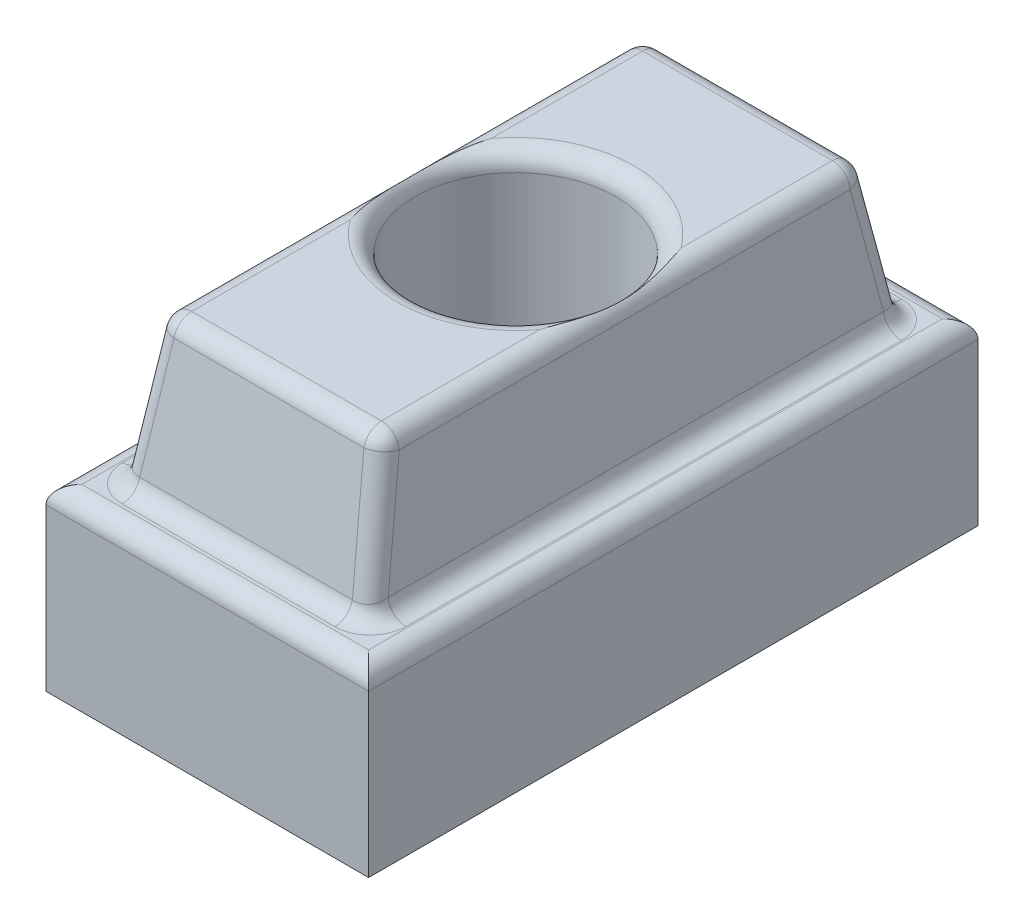
SolidWorks part; units mm, degrees
ref_plane "前视基准面" through (0, 0, 0) normal (0, 0, 1) x (1, 0, 0)
ref_plane "上视基准面" through (0, 0, 0) normal (0, 1, 0) x (1, 0, 0)
ref_plane "右视基准面" through (0, 0, 0) normal (1, 0, 0) x (0, 0, -1)
other "Configuration Table"
sketch "草图1" plane through (0, 0, 0) normal (0, 1, 0) x (1, 0, 0)
  line L0 (14.5065, 0) -> (23.5065, 0)
  line L1 (23.5065, 0) -> (23.5065, 17)
  line L2 (23.5065, 17) -> (14.5065, 17)
  line L3 (14.5065, 17) -> (14.5065, 0)
extrude "凸台-拉伸1" add sketch "草图1" along normal blind 5
sketch "草图2" plane through (0, 0, 0) normal (0, 0, 1) x (1, 0, 0)
  line L1 (14.5065, 5) -> (23.5065, 5) construction
  line L2 (19.0065, 10) -> (22.0065, 10)
  line L4 (22.5065, 5) -> (22.0065, 10)
  line L6 (19.0065, 10) -> (16.0065, 10)
  line L7 (16.0065, 10) -> (15.5065, 5)
  line L8 (15.5065, 5) -> (22.5065, 5)
extrude "凸台-拉伸2" add sketch "草图2" against normal blind 17
sketch "草图3" plane through (0, 10, 0) normal (0, 1, 0) x (1, 0, 0)
  circle A0 centre (19.0065, 8.6) radius 1.6
extrude "切除-拉伸1" cut sketch "草图3" against normal through all
sketch "草图4" plane through (0, 10, 0) normal (0, 1, 0) x (1, 0, 0)
  circle A0 centre (19.0065, 8.6) radius 2.8
extrude "切除-拉伸2" cut sketch "草图4" against normal blind 6
sketch "草图5" plane through (14.5065, 0, 0) normal (-1, 0, 0) x (0, 0, 1)
  line L0 (-17, 5) -> (-16, 5)
  line L1 (-17, 5) -> (0, 5) construction
  line L2 (-17, 5) -> (-17, 10)
  line L3 (-17, 10) -> (-15, 10)
  line L4 (-17, 10) -> (0, 10) construction
  line L5 (-15.2, 9) -> (-16, 5)
  line L6 (0, 5) -> (-1, 5)
  line L7 (0, 5) -> (0, 10)
  line L8 (0, 10) -> (-2, 10)
  line L9 (-1.8, 9) -> (-1, 5)
  line L11 (-8.5, 9) -> (-1.8, 9)
  line L12 (-8.5, 9) -> (-15.2, 9)
  line L13 (-2, 10) -> (-15, 10)
extrude "切除-拉伸3" cut sketch "草图5" against normal through all
fillet "圆角1" radius 0.5 17 edges at (19.0065, 9, -11.4) (19.0065, 9, -1.8) (15.9065, 9, -8.5) (19.0065, 9, -15.2) (22.1065, 9, -8.5) (19.0065, 5, -17) (23.5065, 5, -8.5) (19.0065, 5, 0) (14.5065, 5, -8.5) (19.0065, 5, -16) (15.5065, 5, -8.5) (19.0065, 5, -1) (22.5065, 5, -8.5) (22.3065, 7, -15.6) (22.3065, 7, -1.4) (15.7065, 7, -1.4) (15.7065, 7, -15.6)
